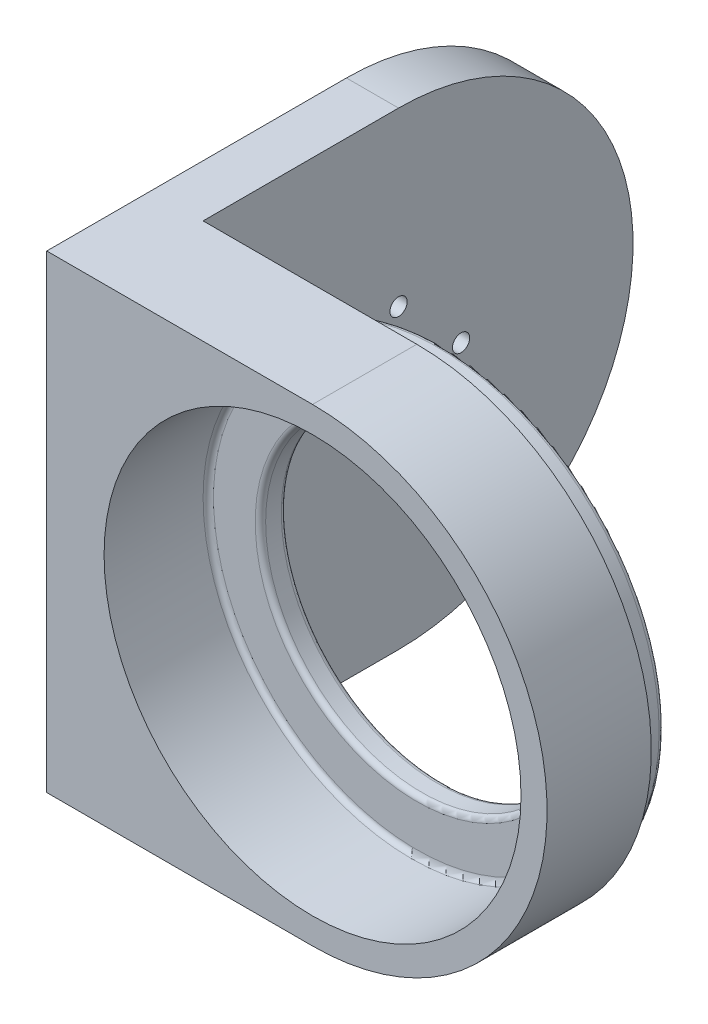
SolidWorks part; units mm, degrees
ref_plane "Front Plane" through (0, 0, 0) normal (0, 0, 1) x (1, 0, 0)
ref_plane "Top Plane" through (0, 0, 0) normal (0, 1, 0) x (1, 0, 0)
ref_plane "Right Plane" through (0, 0, 0) normal (1, 0, 0) x (0, 0, -1)
sketch "Sketch1" plane through (0, 0, 0) normal (0, 0, 1) x (1, 0, 0)
  line L0 (0, 0) -> (-41, 0) construction
  line L4 (0, 45) -> (-41, 45)
  line L5 (-41, 45) -> (-41, -45)
  line L6 (0, -45) -> (-41, -45)
  circle A0 centre (0, 0) radius 40
  arc A1 (0, -45) -> (0, 45) centre (0, 0) ccw
  dimension "D1" = 80
  dimension "D2" = 90
  dimension "D3" = 41
extrude "Boss-Extrude1" add sketch "Sketch1" along normal blind 40
sketch "Sketch6" plane through (0, 0, 0) normal (0, 0, -1) x (-1, 0, 0)
  circle A0 centre (0, 0) radius 99.6758
extrude "Cut-Extrude3" cut sketch "Sketch6" against normal mid plane 40
sketch "Sketch7" plane through (0, 0, 20) normal (0, 0, 1) x (1, 0, 0)
  circle A1 centre (0, 0) radius 42.5
  circle A2 centre (0, 0) radius 30
  dimension "D1" = 60
extrude "Boss-Extrude4" add sketch "Sketch7" against normal blind 5
fillet "Fillet1" radius 1 5 edges at (42.5, 0, 15) (30, 0, 15) (-40, 0, 20) (30, 0, 20) (42.5, 0, 20)
sketch "Sketch8" plane through (-41, 0, 0) normal (-1, 0, 0) x (0, 0, 1)
  line L0 (-17.5, 0) -> (-17.5, 12) construction
  line L4 (40, 45) -> (40, -45)
  line L6 (40, -45) -> (-17.5, -45)
  line L7 (-17.5, 0) -> (-5.5, 0) construction
  line L8 (40, 45) -> (-17.5, 45)
  line L9 (-17.5, 0) -> (-17.5, 10) construction
  arc A12 (-17.5, 45) -> (-17.5, -45) centre (-17.5, 0) ccw
  arc A13 (-22.461, -0.6229) -> (-22.4823, -0.4204) centre (-17.5, 0) ccw construction
  arc A14 (-22.4823, -0.4204) -> (-22.461, -0.6229) centre (-17.5, 0) ccw construction
  arc A15 (-19.1494, 12.0447) -> (-19.0941, 11.574) centre (-17.5, 12) ccw construction
  circle A31 centre (-17.5, 12) radius 1.65
  circle A32 centre (-17.5, 0) radius 5
  circle A33 centre (-5.5, 0) radius 1.65
  circle A34 centre (-17.5, -12) radius 1.65
  circle A35 centre (-29.5, 0) radius 1.65
  point P26 (0, 0)
  point P29 (-17.5, 0)
  point P37 (-17.5, 0)
  dimension "D1" = 45
  dimension "D2" = 57.5
  dimension "D3" = 10
  dimension "D5" = 12
  dimension "D4" = 3.3
  dimension "D6" = 10
  dimension "D7" = 4
extrude "Boss-Extrude5" add sketch "Sketch8" along normal blind 10
